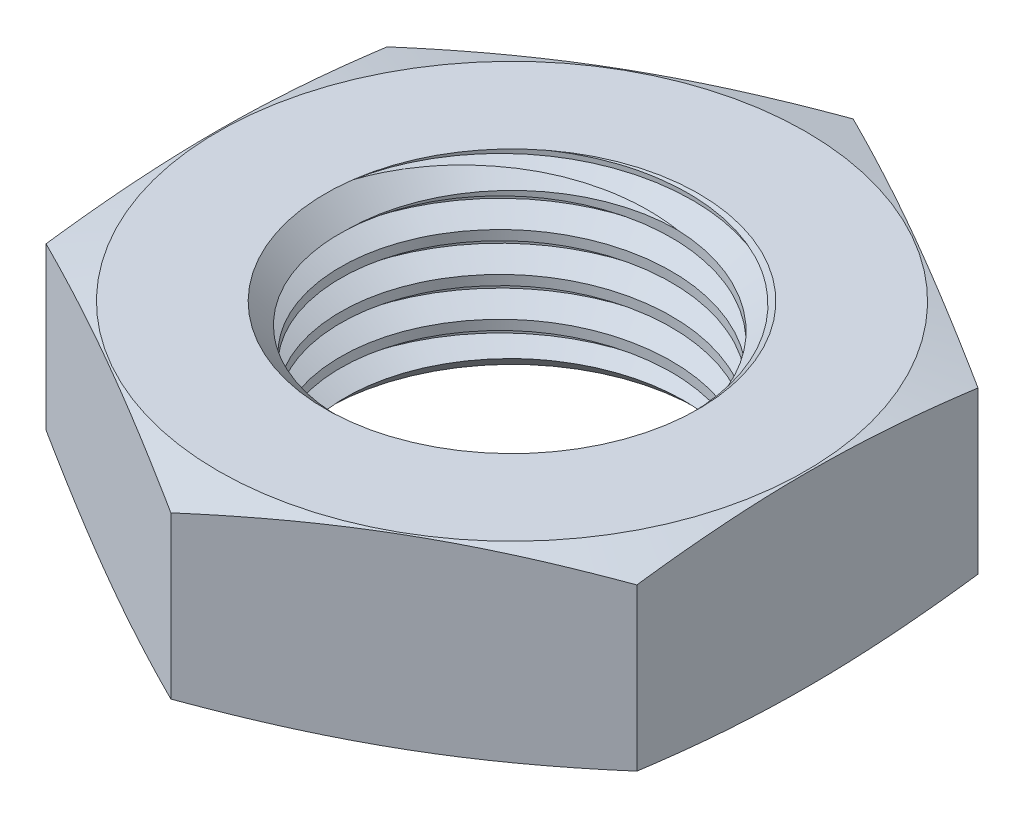
SolidWorks part; units mm, degrees
ref_plane "Front Plane" through (0, 0, 0) normal (0, 0, 1) x (1, 0, 0)
ref_plane "Top Plane" through (0, 0, 0) normal (0, 1, 0) x (1, 0, 0)
ref_plane "Right Plane" through (0, 0, 0) normal (1, 0, 0) x (0, 0, -1)
sketch "Sketch1" plane through (0, 0, 0) normal (0, 0, 1) x (1, 0, 0)
  line L0 (0, 0) -> (9.45, 0)
  line L1 (9.45, 0) -> (20.6462, -3)
  line L2 (20.6462, -3) -> (9.45, -6)
  line L3 (9.45, -6) -> (0, -6)
  line L4 (0, -6) -> (0, 0)
  line L5 (0, -6) -> (0, 0) construction
revolve "Revolve1" add sketch "Sketch1" angle 360 about L5
sketch "Sketch2" plane through (0, 0, 0) normal (0, 1, 0) x (1, 0, 0)
  line L0 (-38, 38) -> (-38, -38)
  line L1 (-38, -38) -> (38, -38)
  line L2 (38, -38) -> (38, 38)
  line L3 (38, 38) -> (-38, 38)
  line L4 (-9.5, -5.4848) -> (0, -10.9697)
  line L5 (0, -10.9697) -> (9.5, -5.4848)
  line L6 (9.5, -5.4848) -> (9.5, 5.4848)
  line L7 (9.5, 5.4848) -> (0, 10.9697)
  line L8 (0, 10.9697) -> (-9.5, 5.4848)
  line L9 (-9.5, 5.4848) -> (-9.5, -5.4848)
extrude "Cut-Extrude1" cut sketch "Sketch2" along normal blind 7 and the other way blind 7
sketch "Sketch3" plane through (0, 0, 0) normal (0, 0, 1) x (1, 0, 0)
  line L0 (0, 0) -> (6, 0)
  line L1 (6, 0) -> (5.3235, -0.6765)
  line L2 (5.3235, -0.6765) -> (5.3235, -5.3235)
  line L3 (5.3235, -5.3235) -> (6, -6)
  line L4 (6, -6) -> (0, -6)
  line L5 (0, -6) -> (0, 0)
  line L6 (0, -6) -> (0, 0) construction
revolve "Cut-Revolve1" cut sketch "Sketch3" angle 360 about L6 reverse direction yes
cosmetic thread "Cosmetic Thread1" parameters "D1"=6, "D2"=12
ref_plane "Plane1" through (0, -3, 0) normal (0, 1, 0) x (1, 0, 0)
ref_plane "2CYL XY" through (0, -3, 0) normal (0, 1, 0) x (1, 0, 0)
ref_plane "2CYL XZ" through (0, 0, 0) normal (0, 0, 1) x (1, 0, 0)
ref_plane "2CYL YZ" through (0, 0, 0) normal (1, 0, 0) x (0, 0, -1)
ref_axis "2CYL X" through (-80.9, -3, 0) along (1, 0, 0)
ref_axis "2CYL Y" through (0, -3, 50) along (0, 0, -1)
ref_axis "2CYL Z" through (0, 50, 0) along (0, -1, 0)
sketch3d "2CYL"
  point P0 (0, -3, 0)
ref_plane "din439b_punkt XY" through (0, 0, 0) normal (0, 1, 0) x (1, 0, 0)
ref_plane "din439b_punkt XZ" through (0, 0, 0) normal (0, 0, 1) x (1, 0, 0)
ref_plane "din439b_punkt YZ" through (0, 0, 0) normal (1, 0, 0) x (0, 0, -1)
ref_axis "din439b_punkt X" through (-80.9, 0, 0) along (1, 0, 0)
ref_axis "din439b_punkt Y" through (0, 0, 50) along (0, 0, -1)
ref_axis "din439b_punkt Z" through (0, 50, 0) along (0, -1, 0)
sketch3d "din439b_punkt"
  point P0 (0, 0, 0)
other "Freeze***"
thread "Thread1" pitch 1.25 method cut profile "Thread Profile1" start angle 0, offset 5, length 25, pitch 1.25, diameter 10.647
ref_plane "Plane2" through (-5.3235, 4.3235, 0) normal (0, 0, 1) x (-1, 0, 0)
sketch "Thread Profile1" plane through (-5.3235, 4.3235, 0) normal (0, 0, 1) x (-1, 0, 0)
  line L0 (0, 0) -> (0, 1.25) construction
  line L1 (0, 0) -> (0.6766, 0.3906)
  line L2 (0.6766, 0.3906) -> (0.6766, 0.5469)
  line L3 (0.6766, 0.5469) -> (0, 0.9375)
  line L4 (0.6766, 0.4687) -> (0, 0.4687) construction
  line L11 (0, 0) -> (0, 0.9375)
  point P2 (0, 0)
  dimension "Pitch" = 1.25
  dimension "Profile_Angle" = 60
  dimension "Profile_Land" = 0.1562
  dimension "Profile_Height" = 0.6766
